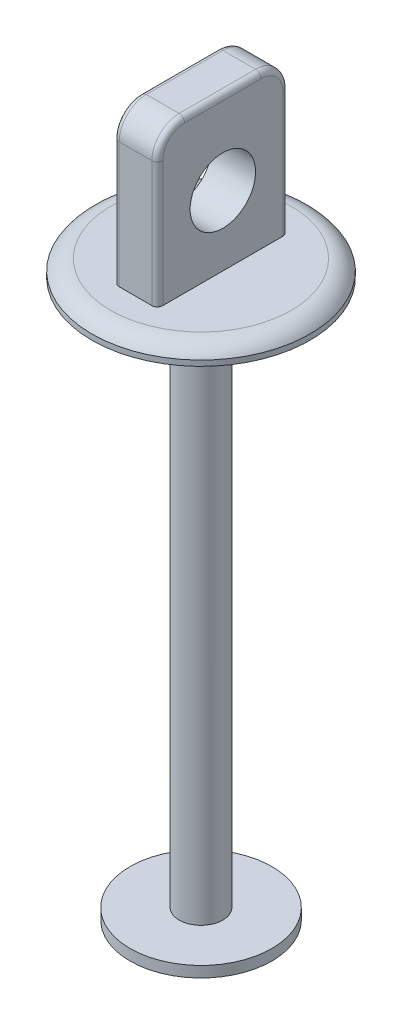
SolidWorks part; units mm, degrees
ref_plane "Front Plane" through (0, 0, 0) normal (0, 0, 1) x (1, 0, 0)
ref_plane "Top Plane" through (0, 0, 0) normal (0, 1, 0) x (1, 0, 0)
ref_plane "Right Plane" through (0, 0, 0) normal (1, 0, 0) x (0, 0, -1)
sketch "Sketch1" plane through (0, 0, 0) normal (0, 1, 0) x (1, 0, 0)
  circle A0 centre (0, 0) radius 13
  dimension "13" = 26
extrude "Boss-Extrude1" add sketch "Sketch1" along normal blind 2
sketch "Sketch2" plane through (0, 2, 0) normal (0, 1, 0) x (1, 0, 0)
  circle A0 centre (0, 0) radius 4
  dimension "D1" = 8
extrude "Boss-Extrude2" add sketch "Sketch2" along normal blind 100
sketch "Sketch3" plane through (0, 102, 0) normal (0, 1, 0) x (1, 0, 0)
  circle A0 centre (0, 0) radius 20
  dimension "D1" = 40
extrude "Boss-Extrude3" add sketch "Sketch3" along normal blind 1
sketch "Sketch4" plane through (0, 102, 0) normal (0, -1, 0) x (1, 0, 0)
  circle A0 centre (0, 0) radius 17
  dimension "D1" = 34
extrude "Boss-Extrude4" add sketch "Sketch4" along normal blind 1
sketch "Sketch5" plane through (0, 103, 0) normal (0, 1, 0) x (1, 0, 0)
  line L1 (4, -12) -> (-4, -12)
  line L2 (4, -12) -> (4, 12)
  line L3 (4, 12) -> (-4, 12)
  line L4 (-4, -12) -> (-4, 12)
  line L5 (4, -12) -> (-4, 12) construction
  line L6 (4, 12) -> (-4, -12) construction
  point P0 (0, 0)
  dimension "D1" = 8
  dimension "D2" = 24
extrude "Boss-Extrude5" add sketch "Sketch5" along normal blind 30
sketch "Sketch6" plane through (0, 103, 0) normal (0, 1, 0) x (1, 0, 0)
  circle A0 centre (0, 0) radius 20
  dimension "D1" = 40
extrude "Boss-Extrude6" add sketch "Sketch6" along normal blind 2 separate body
fillet "Fillet1" radius 4 1 edges at (0, 105, 20)
sketch "Sketch8" plane through (-4, 0, 0) normal (-1, 0, 0) x (0, 0, 1)
  line L0 (0, 133) -> (0, 103) construction
  line L1 (16.5359, 105) -> (-16.5359, 105) construction
  line L4 (-12, 133) -> (12, 133) construction
  circle A0 centre (0, 118) radius 3
  dimension "D1" = 6
  dimension "D2" = 15
  dimension "D3" = 28
ref_plane "Plane1" through (0, 0, 0) normal (-1, 0, 0) x (0, 0, 1)
sketch "Sketch11" plane through (0, 0, 0) normal (-1, 0, 0) x (0, 0, 1)
  line L4 (0, 117.7672) -> (0, 118) construction
  arc A1 (-6, 117.7672) -> (6, 117.7672) centre (0, 117.7672) ccw
  circle A2 centre (0, 117.7672) radius 6
  dimension "D1" = 12
fillet "Fillet3" radius 5 2 edges at (0, 133, -12) (0, 133, 12)
fillet "Fillet4" radius 1 10 edges at (-4, 115.5, -12) (-4, 131.5355, -10.5355) (-4, 133, 0) (-4, 131.5355, 10.5355) (4, 115.5, -12) (4, 131.5355, -10.5355) (4, 133, 0) (4, 131.5355, 10.5355) (-4, 115.5, 12) (4, 115.5, 12)
extrude "Cut-Extrude1" cut sketch "Sketch11" against normal through all both and the other way through all contours A1 A2 region at (0, 117.7672, 0)
